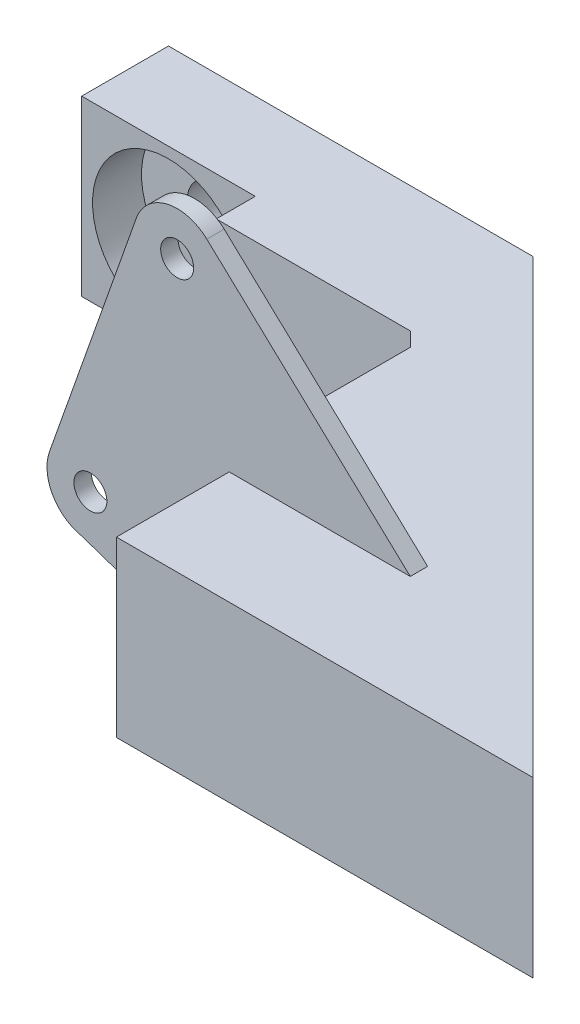
SolidWorks part; units mm, degrees
ref_plane "Front Plane" through (0, 0, 0) normal (0, 0, 1) x (1, 0, 0)
ref_plane "Top Plane" through (0, 0, 0) normal (0, 1, 0) x (1, 0, 0)
ref_plane "Right Plane" through (0, 0, 0) normal (1, 0, 0) x (0, 0, -1)
sketch "Sketch1" plane through (0, 0, 0) normal (0, 1, 0) x (1, 0, 0)
  line L0 (0, 0) -> (273.7383, 0)
  line L1 (0, 0) -> (-341.2497, -341.2497)
  line L2 (0, 0) -> (341.2497, -341.2497)
  line L3 (341.2497, -341.2497) -> (0, -682.4995)
  line L4 (-341.2497, -341.2497) -> (0, -682.4995)
  line L5 (-8.9803, -8.9803) -> (332.2695, -350.23)
  line L6 (-41.275, -60.96) -> (41.275, -60.96)
  line L7 (-41.275, -60.96) -> (-41.275, -86.36)
  line L8 (-41.275, -86.36) -> (41.275, -86.36)
  line L9 (41.275, -60.96) -> (41.275, -86.36)
  line L10 (-41.275, -60.96) -> (41.275, -86.36) construction
  line L11 (-41.275, -86.36) -> (41.275, -60.96) construction
  line L12 (35.3795, -53.34) -> (-12.7, -53.34)
  line L13 (-12.7, -53.34) -> (-12.7, -40.64)
  line L14 (-12.7, -40.64) -> (40.64, -40.64)
  line L15 (43.18, -61.1405) -> (43.18, -87.63)
  line L16 (43.18, -87.63) -> (16.51, -87.63)
  line L17 (16.51, -87.63) -> (16.51, -90.17)
  line L18 (16.51, -90.17) -> (90.17, -90.17)
  line L19 (45.72, -90.17) -> (45.72, -106.68)
  line L20 (6.35, -90.424) -> (44.45, -90.424)
  line L21 (6.35, -90.424) -> (6.35, -100.076)
  line L22 (6.35, -100.076) -> (44.45, -100.076)
  line L23 (44.45, -90.424) -> (44.45, -100.076)
  line L24 (6.35, -90.424) -> (44.45, -100.076) construction
  line L25 (6.35, -100.076) -> (44.45, -90.424) construction
  line L26 (-6.35, -88.9) -> (6.35, -88.9)
  line L27 (-6.35, -88.9) -> (-6.35, -101.6)
  line L28 (-6.35, -101.6) -> (6.35, -101.6)
  line L29 (6.35, -88.9) -> (6.35, -101.6)
  line L30 (-6.35, -88.9) -> (6.35, -101.6) construction
  line L31 (-6.35, -101.6) -> (6.35, -88.9) construction
  line L32 (45.72, -106.68) -> (106.68, -106.68)
  line L33 (6.985, -107.95) -> (-12.7, -107.95)
  line L34 (-12.7, -139.7) -> (121.7395, -139.7)
  line L35 (6.985, -107.95) -> (6.985, -106.68)
  line L36 (6.985, -106.68) -> (45.72, -106.68)
  line L37 (-12.7, -107.95) -> (-12.7, -139.7)
  line L38 (12.7, -53.34) -> (12.7, -59.055)
  line L39 (121.7395, -139.7) -> (143.6841, -161.6446)
  line L40 (143.6841, -161.6446) -> (152.6644, -152.6644)
  line L41 (12.7, -59.055) -> (41.0945, -59.055)
  line L42 (-12.7, -115.57) -> (0, -139.7)
  line L43 (6.985, -106.68) -> (-12.7, -107.95)
  point P4 (0, -73.66)
  point P18 (25.4, -95.25)
  point P26 (0, -95.25)
  point P32 (16.51, -88.9)
  point P47 (88.7195, -106.68)
  point P48 (0, 0)
  dimension "D1" = 482.6
  dimension "D2" = 482.6
  dimension "D3" = 45
  dimension "D4" = 25.4
  dimension "D5" = 82.55
  dimension "D6" = 73.66
  dimension "D7" = 12.7
  dimension "D8" = 12.7
  dimension "D9" = 7.62
  dimension "D10" = 1.905
  dimension "D11" = 1.27
  dimension "D12" = 2.54
  dimension "D13" = 12.7
  dimension "D14" = 12.7
  dimension "D15" = 12.7
  dimension "D16" = 9.652
  dimension "D17" = 9.906
  dimension "D18" = 38.1
  dimension "D19" = 21.59
  dimension "D20" = 25.4
  dimension "D21" = 8.89
  dimension "D22" = 1.27
  dimension "D23" = 16.51
  dimension "D24" = 1.27
  dimension "D25" = 0.635
  dimension "D26" = 31.75
  dimension "D27" = 215.9
  dimension "D28" = 1.905
  dimension "D29" = 12.7
  dimension "D30" = 7.62
  dimension "D31" = 12.7
  dimension "D32" = 12.7
extrude "Boss-Extrude1" add sketch "Sketch1" along normal blind 25.4 contours L14 L13 L12 L5 | L5 L18 L2 L14 | L38 L41 L5 L12 | L17 L18 L5 L15 L16 | L19 L32 L5 L18 | L5 L32 L2 L18 region at (56.4247, 0, 65.405) region at (8.3258, 0, 47.3121) region at (89.4447, 0, 98.425) region at (25.5218, 0, 56.3041) region at (49.6693, 0, 81.6578) region at (63.4191, 0, 99.0788)
ref_axis "Axis1" through (0, 0, 95.25) along (0, 0, -1)
ref_plane "Plane1" through (0, 0, 53.34) normal (0, 0, 1) x (1, 0, 0)
sketch "Sketch2" plane through (0, 0, 53.34) normal (0, 0, 1) x (1, 0, 0)
  line L0 (12.7, 0) -> (-12.7, 0) construction
  circle A0 centre (0, 12.7) radius 11.1125
  circle A1 centre (0, 12.7) radius 4.445
  dimension "D1" = 22.225
  dimension "D3" = 8.89
  dimension "D2" = 12.7
extrude "Cut-Extrude1" cut sketch "Sketch2" against normal blind 7.1628 contours A0
extrude "Cut-Extrude2" cut sketch "Sketch2<3>" against normal up to next contours A1
sketch "Sketch2<3>" plane through (0, 0, 53.34) normal (0, 0, 1) x (1, 0, 0) same geometry as "Sketch2"
extrude "Boss-Extrude2" add sketch "Sketch1<3>" along normal offset from surface (68.58 mm away) 43.18 contours L19 L32 L5 L18 | L17 L18 L5 L15 L16 region at (49.6693, 0, 81.6578) region at (63.4191, 0, 99.0788) up to face at (30.7103, 25.4, 72.0131) offset beyond the face yes
sketch "Sketch1<3>" plane through (0, 0, 0) normal (0, 1, 0) x (1, 0, 0) same geometry as "Sketch1"
ref_plane "Plane2" through (0, 0, 90.17) normal (0, 0, 1) x (1, 0, 0)
sketch "Sketch4" plane through (0, 0, 90.17) normal (0, 0, 1) x (1, 0, 0)
  line L0 (16.51, 0) -> (45.72, 0) construction
  line L1 (22.6021, 6.9996) -> (43.18, 0)
  line L2 (19.4132, 14.8167) -> (32.1132, 50.7377)
  line L3 (41.3885, 54.0532) -> (88.7195, 25.4)
  line L4 (88.7195, 25.4) -> (88.7195, 68.58)
  line L5 (88.7195, 68.58) -> (16.51, 68.58)
  line L6 (16.51, 68.58) -> (16.51, 0)
  line L7 (16.51, 0) -> (45.72, 0)
  circle A0 centre (25.4, 12.7) radius 2.413
  circle A1 centre (38.1, 48.621) radius 2.413
  circle A2 centre (0, 12.7) radius 4.445 construction
  circle A3 centre (0, 12.7) radius 41.275
  circle A4 centre (38.1, 48.621) radius 6.35
  circle A5 centre (25.4, 12.7) radius 6.35
  point P8 (0, 12.7)
  point P29 (0, 0)
  point P30 (0, 0)
  dimension "D5" = 4.826
  dimension "D6" = 82.55
  dimension "D7" = 12.7
  dimension "D8" = 12.7
  dimension "D1" = 38.1
  dimension "D2" = 12.7
  dimension "D3" = 12.7
  dimension "D4" = 25.4
extrude "Cut-Extrude3" cut sketch "Sketch4" against normal up to next contours A1 | A0 region at (25.4, 12.7, 90.17) region at (38.1, 48.621, 90.17)
extrude "Cut-Extrude4" cut sketch "Sketch4<4>" against normal up to next contours A4 L3 L4 L5 L6 A3 L2 | A5 L2 A3 L6 L7 region at (21.9809, 24.1517, 90.17) region at (58.4104, 54.42, 90.17)
sketch "Sketch4<4>" plane through (0, 0, 90.17) normal (0, 0, 1) x (1, 0, 0) same geometry as "Sketch4"
extrude "Cut-Extrude5" cut sketch "Sketch4<7>" along normal up to surface (16.51 mm away) contours A4 L3 L4 L5 L6 A3 L2 | A5 L2 A3 L6 L7 | A3 L7 region at (21.9809, 24.1517, 90.17) region at (40.7002, 0.4009, 90.17) region at (58.4104, 54.42, 90.17) up to face at (80.3732, 31.3267, 106.68)
sketch "Sketch4<7>" plane through (0, 0, 90.17) normal (0, 0, 1) x (1, 0, 0) same geometry as "Sketch4"
extrude "Cut-Extrude7" cut sketch "Sketch4<10>" against normal up to next contours A3 L7 L1 region at (40.7002, 0.4009, 90.17)
sketch "Sketch4<10>" plane through (0, 0, 90.17) normal (0, 0, 1) x (1, 0, 0) same geometry as "Sketch4"
ref_plane "Plane3" through (0, 25.4, 0) normal (0, 1, 0) x (1, 0, 0)
sketch "Sketch7" plane through (0, 25.4, 0) normal (0, 1, 0) x (1, 0, 0)
  line L0 (43.18, -61.1405) -> (43.18, -87.63)
  line L1 (43.18, -87.63) -> (69.6695, -87.63)
  line L2 (88.7195, -106.68) -> (43.18, -61.1405) construction
  line L3 (69.6695, -87.63) -> (43.18, -61.1405)
  line L4 (45.72, -90.17) -> (72.2095, -90.17)
  line L5 (43.18, -61.1405) -> (88.7195, -106.68) construction
  line L6 (72.2095, -90.17) -> (88.7195, -106.68)
  line L7 (88.7195, -106.68) -> (45.72, -106.68)
  line L8 (45.72, -106.68) -> (45.72, -90.17)
extrude "Cut-Extrude8" cut sketch "Sketch7" along normal up to next
sketch "Sketch8" plane through (0, 0, 90.17) normal (0, 0, 1) x (1, 0, 0)
  line L0 (72.2095, 25.4) -> (42.4387, 53.2577)
  line L1 (72.2095, 25.4) -> (72.2095, 35.3948)
  line L2 (72.2095, 35.3948) -> (72.2095, 25.4) construction
  line L3 (41.3885, 54.0532) -> (72.2095, 35.3948) construction
  line L4 (72.2095, 35.3948) -> (41.3885, 54.0532)
  line L5 (69.5409, 27.8971) -> (69.5409, 25.4)
  line L6 (72.2095, 25.4) -> (45.72, 25.4) construction
  line L7 (69.5409, 25.4) -> (72.2095, 25.4)
  circle A0 centre (38.1, 48.621) radius 6.35
  dimension "D1" = 12.7
extrude "Cut-Extrude10" cut sketch "Sketch8" against normal up to next contours A0 L0 L1 L4 region at (62.1227, 38.1699, 90.17)
extrude "Boss-Extrude3" add sketch "Sketch8<3>" against normal up to surface (2.54 mm away) contours L5 L7 L0 region at (70.4304, 26.2324, 90.17) up to face at (40.513, 48.621, 87.63)
sketch "Sketch8<3>" plane through (0, 0, 90.17) normal (0, 0, 1) x (1, 0, 0) same geometry as "Sketch8"
